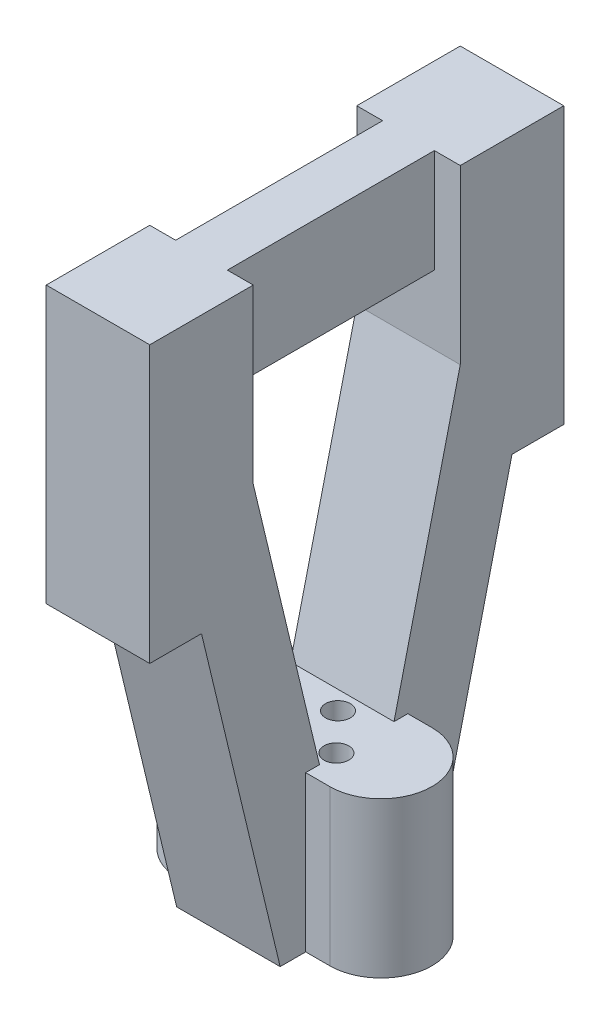
SolidWorks part; units mm, degrees
ref_plane "Front Plane" through (0, 0, 0) normal (0, 0, 1) x (1, 0, 0)
ref_plane "Top Plane" through (0, 0, 0) normal (0, 1, 0) x (1, 0, 0)
ref_plane "Right Plane" through (0, 0, 0) normal (1, 0, 0) x (0, 0, -1)
sketch "Sketch2" plane through (0, 0, 0) normal (1, 0, 0) x (0, 0, -1)
  line L0 (-6, 12.5) -> (-6, 9.5)
  line L1 (-6, 12.5) -> (0, 12.5) construction
  line L2 (-6, 9.5) -> (-4.5, 9.5)
  line L3 (-6, 12.5) -> (-3, 12.5) construction
  line L4 (-3, 12.5) -> (0, 0)
  line L5 (0, 0) -> (-2.22, 0)
  line L6 (-2.22, 0) -> (-4.5, 9.5)
  line L8 (-3, 17.5) -> (-6, 17.5)
  line L9 (-3, 17.5) -> (-3, 12.5)
  line L10 (-3, 12.5) -> (-6, 12.5) construction
  line L11 (-6, 17.5) -> (-6, 12.5)
  dimension "D1" = 6
  dimension "D2" = 3
  dimension "D3" = 1.5
  dimension "D4" = 3
  dimension "D5" = 12.5
  dimension "D6" = 5
extrude "Boss-Extrude2" add sketch "Sketch2" along normal blind 1.5 and the other way blind 1.5
sketch "Sketch1" plane through (0, 0, 0) normal (0, 1, 0) x (1, 0, 0)
  line L0 (-2.2, 0) -> (2.2, 0) construction
  line L1 (-2.2, 0) -> (2.2, 0) construction
  line L2 (-2.2, 1.48) -> (2.2, 1.48)
  line L3 (-2.2, -1.48) -> (2.2, -1.48)
  line L4 (0, 0) -> (0, -6) construction
  line L5 (0.4143, 0.542) -> (1.4512, -0.542) construction
  line L6 (0.9328, 0) -> (-2.25, 0) construction
  line L7 (0.9328, 0) -> (1.8722, 0.8986) construction
  line L8 (0.9328, 0) -> (-0.7293, -1.5898) construction
  line L9 (-2.25, 0) -> (-0.7293, -1.5898) construction
  circle A0 centre (-2.2, 0) radius 0.63 construction
  circle A1 centre (2.2, 0) radius 0.63 construction
  arc A2 (-2.2, 1.48) -> (-2.2, -1.48) centre (-2.2, 0) ccw
  arc A3 (2.2, -1.48) -> (2.2, 1.48) centre (2.2, 0) ccw
  circle A4 centre (-2.25, 0) radius 0.63
  circle A5 centre (0.4143, 0.542) radius 0.36
  circle A6 centre (1.4512, -0.542) radius 0.36
  point P4 (0, 0)
  point P7 (0, 0)
  dimension "D2" = 1.26
  dimension "D3" = 1.48
  dimension "D10" = 0.72
  dimension "D1" = 4.4
  dimension "D4" = 6
  dimension "D6" = 1.5
  dimension "D7" = 3.6
  dimension "D8" = 1.3
  dimension "D9" = 2.2
  dimension "D5" = 2.25
extrude "Boss-Extrude3" add sketch "Sketch1" along normal blind 4.5 contours L3 A3 L2 A2
mirror "Mirror1" about plane through (0, 0, 0) normal (0, 0, 1) of "Boss-Extrude2"
extrude "Cut-Extrude2" cut sketch "Sketch1<3>" along normal through all contours A4 | A5 | A6 region at (-2.25, 0, 0)
sketch "Sketch1<3>" plane through (0, 0, 0) normal (0, 1, 0) x (1, 0, 0) same geometry as "Sketch1"
sketch "Sketch3" plane through (0, 0, -3) normal (0, 0, 1) x (1, 0, 0)
  line L0 (-1.5, 17.5) -> (1.5, 17.5) construction
  line L1 (-0.75, 17.5) -> (0.75, 17.5)
  line L2 (-0.75, 17.5) -> (-0.75, 14.5)
  line L3 (-0.75, 14.5) -> (0.75, 14.5)
  line L4 (0.75, 17.5) -> (0.75, 14.5)
  point P6 (0, 17.5)
  dimension "D1" = 1.5
  dimension "D2" = 3
extrude "Boss-Extrude4" add sketch "Sketch3" along normal up to next
equation "\"TubingOD\"= 1.26"
equation "\"ConcentricDepth\"= 4.5mm"
equation "\"D2@Sketch1\"=\"TubingOD\""
equation "\"D1@Boss-Extrude3\"=\"ConcentricDepth\""
